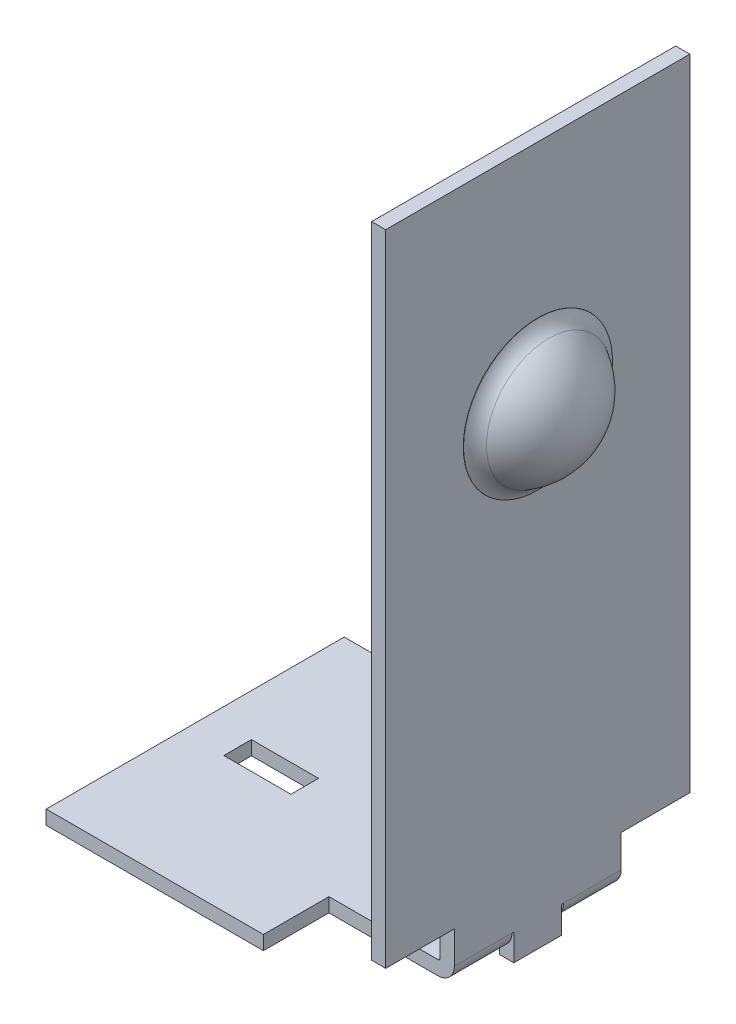
SolidWorks part; units mm, degrees
material "Saf Altın"
ref_plane "Ön Düzlem" through (0, 0, 0) normal (0, 0, 1) x (1, 0, 0)
ref_plane "Üst Düzlem" through (0, 0, 0) normal (0, 1, 0) x (1, 0, 0)
ref_plane "Sağ Düzlem" through (0, 0, 0) normal (1, 0, 0) x (0, 0, -1)
sketch "Çizim1" plane through (0, 0, 0) normal (0, 0, 1) x (1, 0, 0)
  line L0 (-0.3, 0.35) -> (-0.3, 13.55) construction
  line L1 (-0.3, 0.35) -> (-0.3, 14.676)
  line L2 (-36.2839, 13.5501) -> (-36.2839, 0.3548) construction
  line L3 (0, 0.35) -> (0, 13.55) construction
  line L8 (-0.35, 0.3) -> (-7.3, 0.3)
  line L9 (-0.35, 0) -> (-7.3, 0)
  line L10 (0, 0.35) -> (0, 14.676)
  line L13 (-7.3, 0.3) -> (-7.3, 0)
  line L15 (-0.3, 14.676) -> (0, 14.676)
  line L21 (-36.2839, 0.0035) -> (-36.2839, -0.2248) construction
  line L22 (-36.2839, -0.2248) -> (-35.9791, -0.2195) construction
  line L23 (-35.9791, -0.2195) -> (-35.9791, 0.3548) construction
  line L24 (-43.2308, 0) -> (-38.6025, 0) construction
  line L25 (-38.6025, 0) -> (-38.6025, 0.3048) construction
  line L26 (-38.6025, 0.3048) -> (-43.2308, 0.3048) construction
  line L27 (-43.2308, 0.3048) -> (-43.2308, 0) construction
  line L28 (-36.2839, 1.0419) -> (-36.2839, 0.3548) construction
  line L29 (-36.3339, 0.3048) -> (-38.6025, 0.3048) construction
  line L30 (-38.6025, 0.3048) -> (-38.6025, 0) construction
  line L31 (-38.6025, 0) -> (-36.3339, 0) construction
  line L32 (-35.9791, 0.3548) -> (-35.9791, 1.0419) construction
  line L33 (-35.9791, 1.0419) -> (-36.2839, 1.0419) construction
  line L34 (-35.9791, 1.0419) -> (-35.9791, 13.5501) construction
  line L35 (-34.4379, 13.9448) -> (-32.3807, 10.1913) construction
  line L36 (-32.3088, 9.9105) -> (-32.3088, 7.112) construction
  line L37 (-32.3088, 7.112) -> (-32.004, 7.112) construction
  line L38 (-32.004, 7.112) -> (-32.004, 9.9105) construction
  line L39 (-32.1134, 10.3378) -> (-34.1706, 14.0913) construction
  line L40 (-36.2839, 13.5501) -> (-36.2839, 1.0419) construction
  line L41 (-36.2839, 1.0419) -> (-35.9791, 1.0419) construction
  line L42 (1.8134, 14.0912) -> (3.8707, 10.3381) construction
  line L43 (3.9803, 9.9103) -> (3.9803, 7.1103) construction
  line L44 (1.5503, 13.947) -> (3.6076, 10.1939) construction
  line L45 (3.6803, 9.9103) -> (3.6803, 7.1103) construction
  arc A2 (-0.3, 0.35) -> (-0.35, 0.3) centre (-0.35, 0.35) cw
  arc A3 (0, 0.35) -> (-0.35, 0) centre (-0.35, 0.35) cw
  arc A7 (-36.2839, 0.0035) -> (-35.9791, 0.3548) centre (-36.3339, 0.3548) ccw construction
  arc A8 (-36.3339, 0.3048) -> (-36.2839, 0.3548) centre (-36.3339, 0.3548) ccw construction
  arc A9 (-36.3339, 0) -> (-35.9791, 0.3548) centre (-36.3339, 0.3548) ccw construction
  arc A10 (-34.4379, 13.9448) -> (-35.9791, 13.5501) centre (-35.158, 13.5501) ccw construction
  arc A11 (-32.3088, 9.9105) -> (-32.3807, 10.1913) centre (-32.893, 9.9105) ccw construction
  arc A12 (-32.004, 9.9105) -> (-32.1134, 10.3378) centre (-32.893, 9.9105) ccw construction
  arc A13 (-34.1706, 14.0913) -> (-36.2839, 13.5501) centre (-35.158, 13.5501) ccw construction
  arc A14 (3.6076, 10.1939) -> (3.6803, 9.9103) centre (3.0903, 9.9103) cw construction
  arc A15 (3.8707, 10.3381) -> (3.9803, 9.9103) centre (3.0903, 9.9103) cw construction
  arc A16 (0, 13.55) -> (1.5503, 13.947) centre (0.826, 13.55) cw construction
  arc A17 (-0.3, 13.55) -> (1.8134, 14.0912) centre (0.826, 13.55) cw construction
  point P57 (0, 0)
  dimension "D5" = 1.1259
  dimension "D8" = 0.889
  dimension "D15" = 0.05
  dimension "D1" = 13.5501
  dimension "D2" = 14.676
  dimension "D3" = 13.1953
  dimension "D4" = 13.1953
  dimension "D9" = 4.2802
  dimension "D12" = 2.7985
  dimension "D14" = 6.9469
  dimension "D16" = 6.95
  dimension "D17" = 0.3
extrude "Yükseklik-Ekstrüzyon1" add sketch "Çizim1" along normal mid plane 6.48
sketch "Çizim2" plane through (0, 0, 0) normal (0, 1, 0) x (1, 0, 0)
  line L1 (-7.3, -3.24) -> (-7.3, 3.24) construction
  line L3 (0, -4) -> (0, -1.778)
  line L4 (0, 4) -> (-8, 4)
  line L5 (-8, 4) -> (-8, -4)
  line L6 (-8, -4) -> (0, -4)
  line L7 (0, 1.778) -> (0, 4)
  line L13 (-2.6717, 1.778) -> (-2.6717, 3.175)
  line L14 (0, 1.778) -> (-2.6717, 1.778)
  line L15 (-2.6717, 3.175) -> (-7.3, 3.175)
  line L16 (-7.3, 3.175) -> (-7.3, -3.175)
  line L17 (-7.3, -3.175) -> (-2.6717, -3.175)
  line L18 (-2.6717, -3.175) -> (-2.6717, -1.778)
  line L19 (-2.6717, -1.778) -> (0, -1.778)
  line L20 (-4.966, -0.2942) -> (-4.966, 0.2942)
  line L21 (-4.966, 0.2942) -> (-6.396, 0.2942)
  line L22 (-6.396, 0.2942) -> (-6.396, -0.2942)
  line L23 (-6.396, -0.2942) -> (-4.966, -0.2942)
  point P1 (0, 0)
  point P18 (-4.966, 0)
  dimension "D1" = 0.5883
  dimension "D2" = 1.43
  dimension "D3" = 4.6283
  dimension "D5" = 1.397
  dimension "D6" = 1.397
  dimension "D7" = 6.35
  dimension "D8" = 0.904
  dimension "D9" = 2.8808
  dimension "D4" = 4
  dimension "D10" = 8
  dimension "D11" = 8
extrude "Kes-Ekstrüzyon1" cut sketch "Çizim2" along normal blind 1.0419
sketch "Çizim4" plane through (0, 0, 0) normal (1, 0, 0) x (0, 0, -1)
  line L0 (-1.778, 0.35) -> (1.778, 0.35) construction
  line L1 (-0.55, -0.15) -> (0.55, -0.15)
  line L2 (-0.55, -0.15) -> (-0.55, 0.33)
  line L3 (-0.53, 0.35) -> (0.53, 0.35)
  line L4 (0.55, -0.15) -> (0.55, 0.33)
  arc A0 (0.53, 0.35) -> (0.55, 0.33) centre (0.53, 0.33) cw
  arc A1 (-0.55, 0.33) -> (-0.53, 0.35) centre (-0.53, 0.33) cw
  dimension "D4" = 0.02
  dimension "D1" = 1.1
  dimension "D2" = 0.55
  dimension "D3" = 0.5
extrude "Kes-Ekstrüzyon2" cut sketch "Çizim4" against normal blind 0.5
sketch "Çizim5" plane through (0, 0, 0) normal (1, 0, 0) x (0, 0, -1)
  line L0 (0.53, 0.35) -> (-0.53, 0.35) construction
  line L1 (-0.51, -0.22) -> (0.51, -0.22)
  line L2 (-0.51, -0.22) -> (-0.51, 0.33)
  line L3 (-0.53, 0.35) -> (0.53, 0.35)
  line L4 (0.51, -0.22) -> (0.51, 0.33)
  line L5 (-0.51, -0.22) -> (0.51, 0.35) construction
  line L6 (-0.51, 0.35) -> (0.51, -0.22) construction
  line L7 (-1.778, 0.35) -> (-0.53, 0.35) construction
  arc A0 (-0.53, 0.35) -> (-0.51, 0.33) centre (-0.53, 0.33) cw
  arc A1 (0.53, 0.35) -> (0.51, 0.33) centre (0.53, 0.33) ccw
  point P0 (0, 0.065)
  point P17 (0, 0)
  dimension "D1" = 1.02
  dimension "D2" = 0.57
  dimension "D3" = 0.02
extrude "Yükseklik-Ekstrüzyon2" add sketch "Çizim5" against normal blind 0.3
sketch "Çizim6" plane through (0, 0, 0) normal (0, 0, 1) x (1, 0, 0)
  line L0 (-0.3, 8.2677) -> (3, 8.2677) construction
  line L1 (3, 8.2677) -> (3, 11.4283) construction
  line L2 (3, 11.4283) -> (-2.9904, 11.4283) construction
  line L3 (0.716, 9.8408) -> (1.0208, 9.8408)
  line L4 (-0.3, 14.676) -> (-0.3, 1.0419) construction
  line L5 (-0.3, 11.4283) -> (0.0048, 11.4283)
  line L11 (0.0048, 8.2677) -> (0.0048, 11.4283) construction
  line L13 (-0.3, 11.4283) -> (-0.3, 8.2677) construction
  arc A13 (-0.3, 11.4283) -> (-0.2789, 11.3169) centre (0.0048, 11.4283) ccw
  arc A14 (-0.2789, 11.3169) -> (0.0875, 10.9009) centre (0.4776, 11.614) ccw
  arc A15 (0.0048, 11.4283) -> (0.2338, 11.1683) centre (0.4776, 11.614) ccw
  arc A16 (1.0208, 9.8408) -> (0.2338, 11.1683) centre (-0.4924, 9.8408) ccw
  arc A17 (0.716, 9.8408) -> (0.0875, 10.9009) centre (-0.4924, 9.8408) ccw
  point P2 (0, 0)
  dimension "D3" = 1.2084
  dimension "D1" = 0.8128
  dimension "D2" = 0.508
  dimension "D4" = 0.3048
  dimension "D5" = 1.5132
  dimension "D6" = 1.5875
  dimension "D7" = 0.1924
  dimension "D8" = 3.1606
  dimension "D9" = 9.8408
  dimension "D10" = 3
sketch "Çizim7" plane through (0, 0, 0) normal (1, 0, 0) x (0, 0, -1)
  line L0 (0, 11.4283) -> (0, 8.2677) construction
  line L1 (0, 11.4283) -> (0, 8.2677) construction
  circle A0 centre (0, 9.848) radius 1.5803
extrude "Kes-Ekstrüzyon3" cut sketch "Çizim7" against normal blind 0.3
ref_axis "Eksen1" through (-0.4924, 9.8408, 0) along (1, 0, 0)
revolve "Döndür1" add sketch "Çizim6" angle 360 about axis through (-0.4924, 9.8408, 0) along (1, 0, 0)
equation "\"D10@Çizim2\"=2*\"D4@Çizim2\""
equation "\"D2@Çizim4\"=\"D1@Çizim4\"/2"
